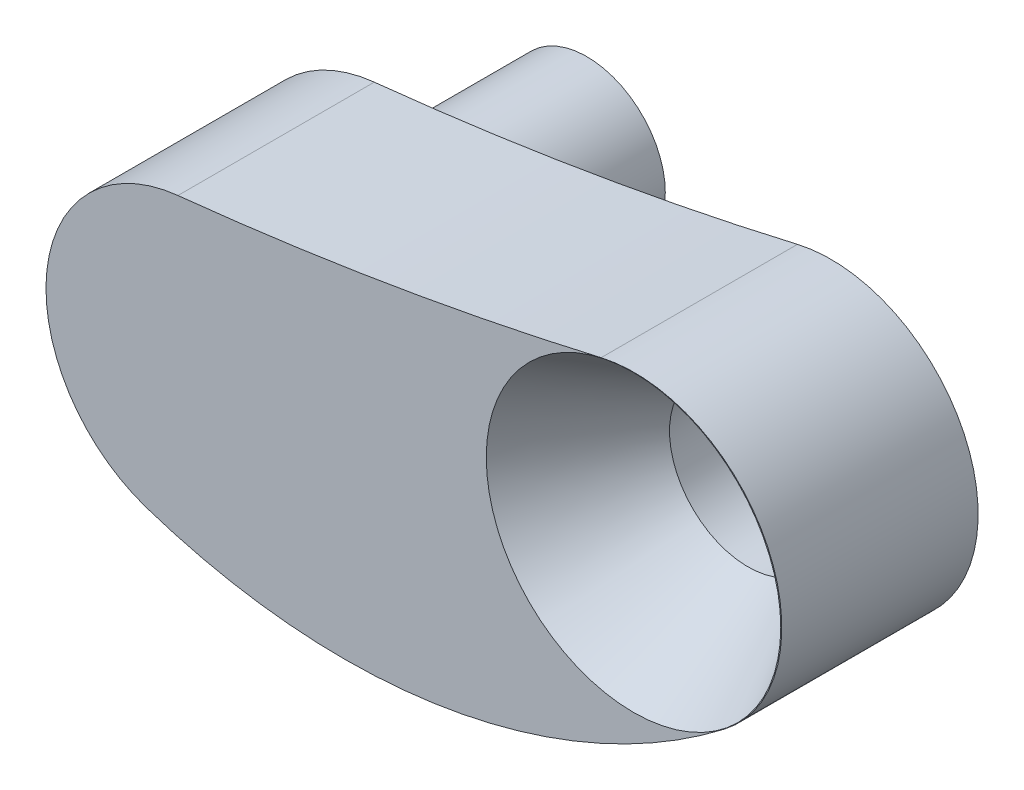
SolidWorks part; units mm, degrees
material "6061 合金"
ref_plane "前视基准面" through (0, 0, 0) normal (0, 0, 1) x (1, 0, 0)
ref_plane "上视基准面" through (0, 0, 0) normal (0, 1, 0) x (1, 0, 0)
ref_plane "右视基准面" through (0, 0, 0) normal (1, 0, 0) x (0, 0, -1)
other "Configuration Table"
sketch "草图1" plane through (0, 0, 0) normal (0, 0, 1) x (1, 0, 0)
  line L1 (0, 0) -> (11.7684, -24.8547) construction
  line L2 (0, 0) -> (8.97, -25.996) construction
  line L3 (0, 0) -> (0.0178, -27.5) construction
  line L4 (-2.9821, -27.1727) -> (0, 0) construction
  circle A0 centre (0, 0) radius 27.5 construction
  arc A1 (-0.3116, -24.5162) -> (-0.9513, -30.3452) centre (0, -27.5) ccw
  circle A2 centre (8.97, -25.996) radius 1.6
  arc A3 (10.8203, -28.3665) -> (8.3099, -23.067) centre (8.991, -25.9887) ccw
  arc A4 (-0.3116, -24.5162) -> (8.3099, -23.067) centre (-7.5818, 45.1052) ccw
  arc A5 (-0.9513, -30.3452) -> (10.8203, -28.3665) centre (3.0761, -18.2999) ccw
  circle A6 centre (0.0178, -27.5) radius 1.6 construction
  point P16 (22.4919, -16.2195)
  point P19 (-0.8944, -24.596)
  dimension "D1" = 55
  dimension "D2" = 6
  dimension "D5" = 3.2
  dimension "D6" = 6
  dimension "D7" = 70
  dimension "D9" = 3.2
  dimension "D3" = 6.3
  dimension "D4" = 6.3
  dimension "D10" = 19
extrude "凸台-拉伸1" add sketch "草图1" along normal blind 4 contours A1 A5 A3 A4 A2 region at (4.1194, -27.1839, 0)
sketch "草图2" plane through (0, 0, 0) normal (0, 0, 1) x (1, 0, 0)
  circle A0 centre (0.0178, -27.5) radius 1.6
  point P3 (0, -27.5)
  point P4 (3.8046, -27.2392)
  point P5 (6.4137, -26.7416)
  dimension "D1" = 3.2
extrude "凸台-拉伸2" add sketch "草图2" against normal blind 4
ref_axis "基准轴1" through (8.97, -25.996, 4) along (0, 0, -1)
ref_plane "基准面1" through (0, -25.996, 0) normal (0, 1, 0) x (1, 0, 0)
sketch "草图3" plane through (0, -25.996, 0) normal (0, 1, 0) x (1, 0, 0)
  line L0 (8.97, -2.5) -> (8.97, -4) construction
  line L1 (8.97, -4) -> (8.97, 0) construction
  line L7 (8.97, 0) -> (8.97, -4) construction
  line L8 (8.3099, 0) -> (-0.3116, 0) construction
  line L9 (8.97, -4) -> (5.97, -4)
  line L10 (-0.3116, -4) -> (8.3099, -4) construction
  line L11 (5.97, -4) -> (7.47, -1.5)
  line L12 (7.47, -1.5) -> (8.97, -1.5)
  line L13 (8.97, -1.5) -> (8.97, -4)
  dimension "D1" = 6
  dimension "D2" = 2.5
  dimension "D3" = 3
revolve "切除-旋转1" cut sketch "草图3" angle 360 about L13
